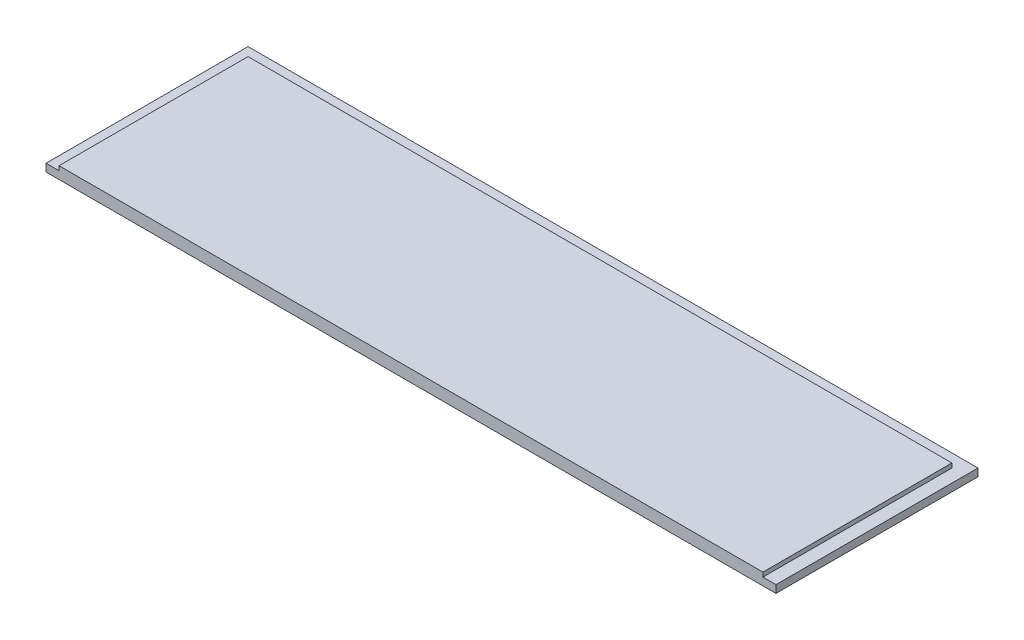
SolidWorks part; units mm, degrees
material "Cedar"
ref_plane "Front Plane" through (0, 0, 0) normal (0, 0, 1) x (1, 0, 0)
ref_plane "Top Plane" through (0, 0, 0) normal (0, 1, 0) x (1, 0, 0)
ref_plane "Right Plane" through (0, 0, 0) normal (1, 0, 0) x (0, 0, -1)
sketch "Sketch1" plane through (0, 0, 0) normal (0, 1, 0) x (1, 0, 0)
  line L1 (-533.4, -147.6375) -> (533.4, -147.6375)
  line L2 (-533.4, -147.6375) -> (-533.4, 147.6375)
  line L3 (-533.4, 147.6375) -> (533.4, 147.6375)
  line L4 (533.4, -147.6375) -> (533.4, 147.6375)
  line L5 (-533.4, -147.6375) -> (533.4, 147.6375) construction
  line L6 (-533.4, 147.6375) -> (533.4, -147.6375) construction
  point P0 (0, 0)
  dimension "D1" = 1066.8
  dimension "D2" = 295.275
extrude "Boss-Extrude1" add sketch "Sketch1" along normal blind 17.4752
sketch "Sketch2" plane through (0, 17.4752, 0) normal (0, 1, 0) x (1, 0, 0)
  line L0 (533.4, 147.6375) -> (-533.4, 147.6375) construction
  line L1 (-533.4, -147.6375) -> (-514.35, -147.6375)
  line L2 (-533.4, -147.6375) -> (-533.4, 147.6375)
  line L4 (-514.35, -147.6375) -> (-514.35, 128.5875)
  line L5 (0, 128.5875) -> (0, 147.6375) construction
  line L6 (-533.4, 147.6375) -> (533.4, 147.6375)
  line L8 (-514.35, 128.5875) -> (514.35, 128.5875)
  line L11 (514.35, 128.5875) -> (514.35, -147.6375)
  line L12 (514.35, -147.6375) -> (533.4, -147.6375)
  line L13 (533.4, 147.6375) -> (533.4, -147.6375)
  point P14 (531.4289, 147.6375)
  dimension "D1" = 19.05
extrude "Cut-Extrude1" cut sketch "Sketch2" against normal blind 6.35
